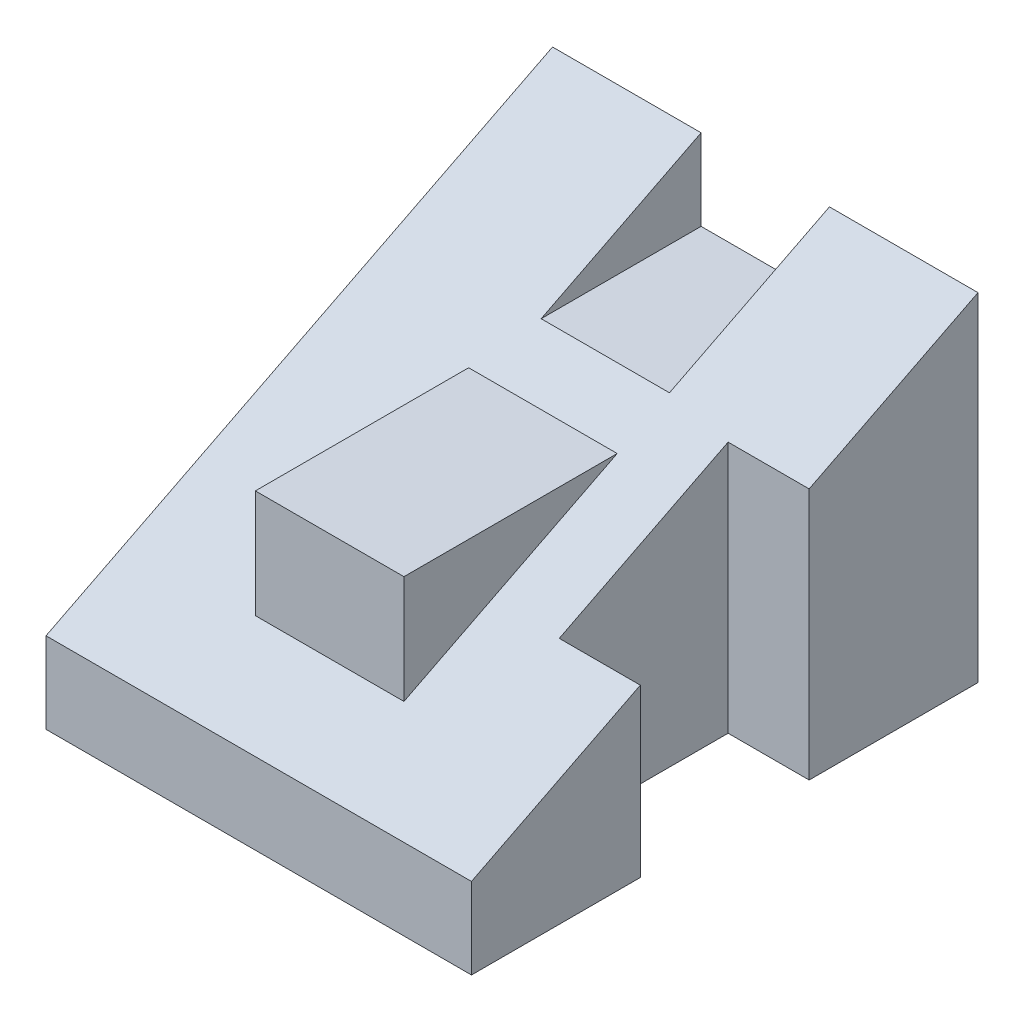
SolidWorks part; units mm, degrees
ref_plane "Front Plane" through (0, 0, 0) normal (0, 0, 1) x (1, 0, 0)
ref_plane "Top Plane" through (0, 0, 0) normal (0, 1, 0) x (1, 0, 0)
ref_plane "Right Plane" through (0, 0, 0) normal (1, 0, 0) x (0, 0, -1)
sketch "Sketch1" plane through (0, 0, 0) normal (1, 0, 0) x (0, 0, -1)
  line L0 (0, 0) -> (0, 50)
  line L1 (0, 50) -> (-75, 12)
  line L2 (-75, 12) -> (-75, 0)
  line L3 (-75, 0) -> (0, 0)
  line L4 (-25, 37.3333) -> (-25, 0)
  line L5 (-50, 24.6667) -> (-50, 0)
  line L6 (-23.6842, 38) -> (0, 38)
  line L7 (-31.4211, 34.08) -> (-63, 34.08)
  line L8 (-63, 34.08) -> (-63, 18.08)
  point P16 (-49.5652, 0)
  dimension "D1" = 12
  dimension "D2" = 25
  dimension "D3" = 75
  dimension "D4" = 25
  dimension "D5" = 50
  dimension "D6" = 12
  dimension "D7" = 16
  dimension "D8" = 12
extrude "Boss-Extrude1" add sketch "Sketch1" along normal blind 63 contours L5 L1 L2 L3 | L6 L1 L4 L3 L0 region at (0, 18.9913, 12.4944) region at (0, 9.5313, 61.0606)
extrude "Boss-Extrude2" add sketch "Sketch1<3>" along normal blind 51 contours L1 L5 L3 L4 region at (0, 15.7157, 36.6487)
sketch "Sketch1<3>" plane through (0, 0, 0) normal (1, 0, 0) x (0, 0, -1) same geometry as "Sketch1"
extrude "Boss-Extrude3" add sketch "Sketch1<4>" along normal blind 22 contours L1 L6 L0 region at (0, 42, 7.8947)
sketch "Sketch1<4>" plane through (0, 0, 0) normal (1, 0, 0) x (0, 0, -1) same geometry as "Sketch1"
extrude "Boss-Extrude4" add sketch "Sketch1<5>" along normal blind 22 from offset 41 contours L1 L6 L0 region at (0, 42, 7.8947)
sketch "Sketch1<5>" plane through (0, 0, 0) normal (1, 0, 0) x (0, 0, -1) same geometry as "Sketch1"
extrude "Boss-Extrude5" add sketch "Sketch1<6>" along normal blind 22 from offset 19 contours L7 L8 L1 region at (0, 28.7467, 52.4737)
sketch "Sketch1<6>" plane through (0, 0, 0) normal (1, 0, 0) x (0, 0, -1) same geometry as "Sketch1"
